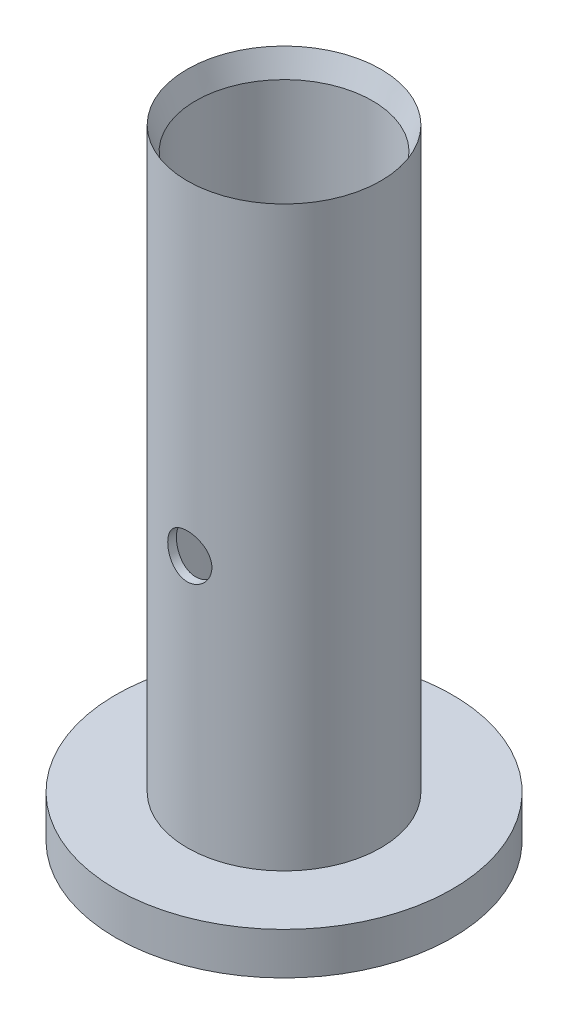
SolidWorks part; units mm, degrees
ref_plane "Front Plane" through (0, 0, 0) normal (0, 0, 1) x (1, 0, 0)
ref_plane "Top Plane" through (0, 0, 0) normal (0, 1, 0) x (1, 0, 0)
ref_plane "Right Plane" through (0, 0, 0) normal (1, 0, 0) x (0, 0, -1)
sketch "Sketch1" plane through (0, 0, 0) normal (0, 1, 0) x (1, 0, 0)
  circle A0 centre (0, 0) radius 20
  dimension "D1" = 40
extrude "Boss-Extrude1" add sketch "Sketch1" along normal blind 5 contours A0
sketch "Sketch2" plane through (0, 5, 0) normal (0, 1, 0) x (1, 0, 0)
  circle A0 centre (0, 0) radius 10.5
  circle A1 centre (0, 0) radius 11.5
  dimension "D1" = 21
  dimension "D2" = 1
extrude "Boss-Extrude2" add sketch "Sketch2" along normal blind 70
sketch "Sketch3" plane through (0, 0, 0) normal (0, 0, 1) x (1, 0, 0)
  line L0 (0, 0) -> (0, 35)
  circle A0 centre (0, 35) radius 2.625
  dimension "D2" = 5.25
  dimension "D1" = 35
extrude "Cut-Extrude1" cut sketch "Sketch3" along normal through all contours A0 region at (1.8037, 33.1963, 0)
chamfer "Chamfer1" distance 1.5 angle 70 1 edges at (0, 75, 10.5) first distance on face at (0, 75, 11.5)
